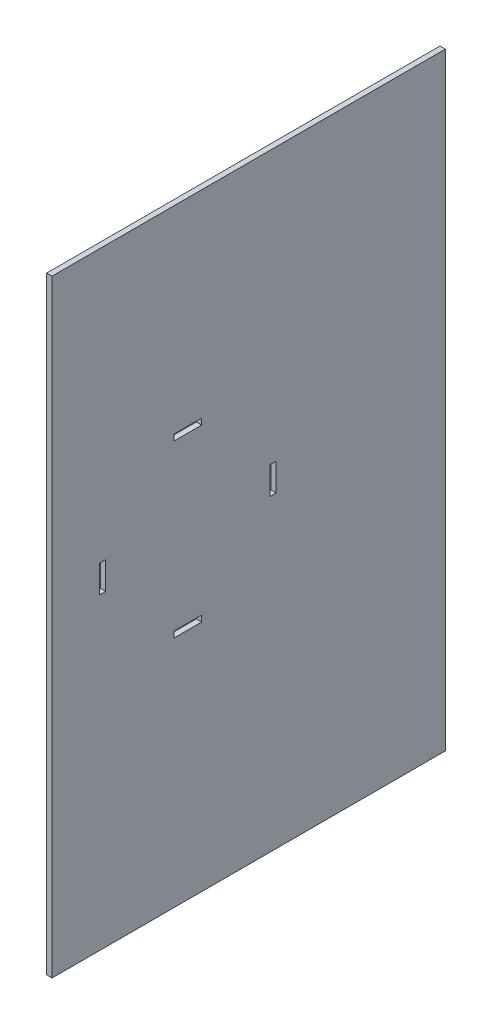
SolidWorks part; units mm, degrees
ref_plane "Front Plane" through (0, 0, 0) normal (0, 0, 1) x (1, 0, 0)
ref_plane "Top Plane" through (0, 0, 0) normal (0, 1, 0) x (1, 0, 0)
ref_plane "Right Plane" through (0, 0, 0) normal (1, 0, 0) x (0, 0, -1)
sketch "Sketch1" plane through (0, 0, 0) normal (1, 0, 0) x (0, 0, -1)
  line L1 (0, 0) -> (110, 0)
  line L2 (0, 0) -> (0, 170)
  line L3 (0, 170) -> (110, 170)
  line L4 (110, 0) -> (110, 170)
  line L18 (38, 90) -> (38, 113.8504) construction
  line L20 (34.15, 113.0004) -> (41.85, 113.0004)
  line L21 (34.15, 113.0004) -> (34.15, 114.7004)
  line L22 (34.15, 114.7004) -> (41.85, 114.7004)
  line L23 (41.85, 113.0004) -> (41.85, 114.7004)
  line L24 (34.15, 113.0004) -> (41.85, 114.7004) construction
  line L25 (34.15, 114.7004) -> (41.85, 113.0004) construction
  line L26 (61.0004, 93.85) -> (61.0004, 86.15)
  line L27 (61.0004, 93.85) -> (62.7004, 93.85)
  line L28 (62.7004, 93.85) -> (62.7004, 86.15)
  line L29 (61.0004, 86.15) -> (62.7004, 86.15)
  line L30 (41.85, 66.9996) -> (34.15, 66.9996)
  line L31 (41.85, 66.9996) -> (41.85, 65.2996)
  line L32 (41.85, 65.2996) -> (34.15, 65.2996)
  line L33 (34.15, 66.9996) -> (34.15, 65.2996)
  line L34 (14.9996, 86.15) -> (14.9996, 93.85)
  line L35 (14.9996, 86.15) -> (13.2996, 86.15)
  line L36 (13.2996, 86.15) -> (13.2996, 93.85)
  line L37 (14.9996, 93.85) -> (13.2996, 93.85)
  circle A1 centre (38, 90) radius 23.8504 construction
  point P28 (38, 90)
  dimension "D1" = 4
  dimension "D6" = 47.7008
  dimension "D3" = 90
  dimension "D4" = 170
  dimension "D5" = 110
  dimension "D7" = 38
  dimension "D8" = 1.7
  dimension "D9" = 7.7
extrude "Boss-Extrude1" add sketch "Sketch1" along normal blind 1.5
